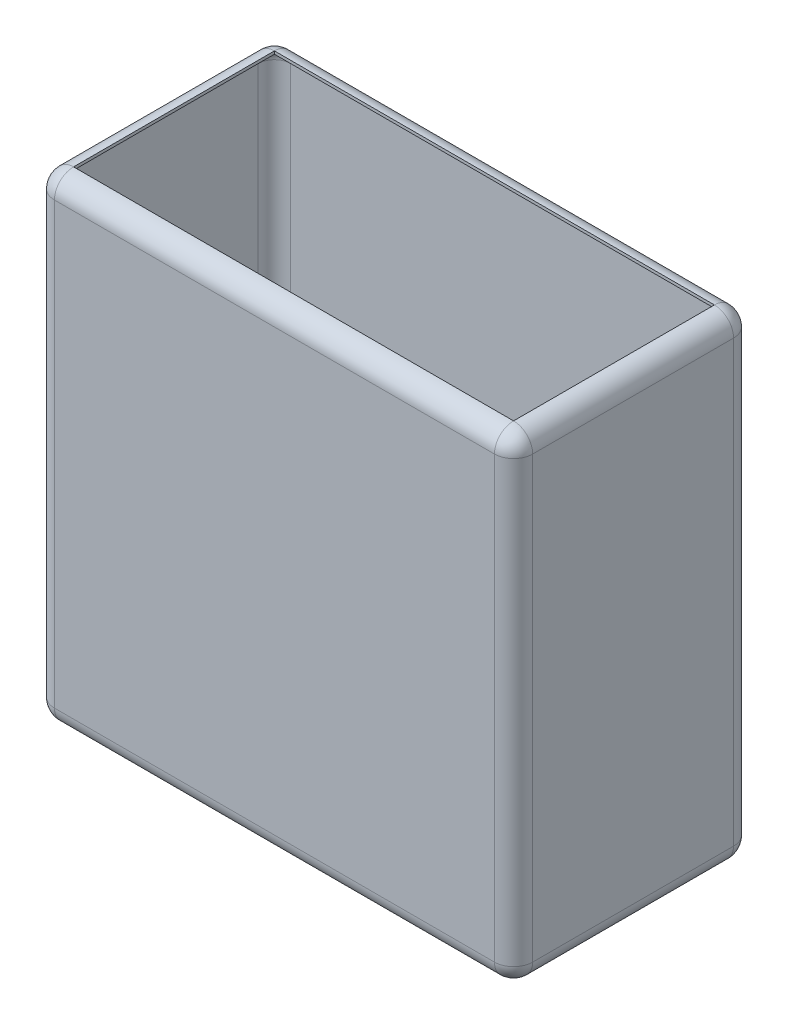
SolidWorks part; units mm, degrees
ref_plane "Alzado" through (0, 0, 0) normal (0, 0, 1) x (1, 0, 0)
ref_plane "Planta" through (0, 0, 0) normal (0, 1, 0) x (1, 0, 0)
ref_plane "Vista lateral" through (0, 0, 0) normal (1, 0, 0) x (0, 0, -1)
sketch "Croquis1" plane through (0, 0, 0) normal (0, 1, 0) x (1, 0, 0)
  line L1 (250, -125) -> (-250, -125)
  line L2 (250, -125) -> (250, 125)
  line L3 (250, 125) -> (-250, 125)
  line L4 (-250, -125) -> (-250, 125)
  line L5 (250, -125) -> (-250, 125) construction
  line L6 (250, 125) -> (-250, -125) construction
  point P0 (0, 0)
  dimension "D1" = 500
  dimension "D2" = 250
extrude "Extruir1" add sketch "Croquis1" along normal blind 500
fillet "Redondeo1" radius 20 12 edges at (0, 500, -125) (250, 500, 0) (0, 500, 125) (-250, 500, 0) (0, 0, 125) (250, 0, 0) (0, 0, -125) (-250, 0, 0) (-250, 250, -125) (250, 250, -125) (250, 250, 125) (-250, 250, 125)
shell "Vaciado1" thickness 3 removed face at (0, 500, 0)
